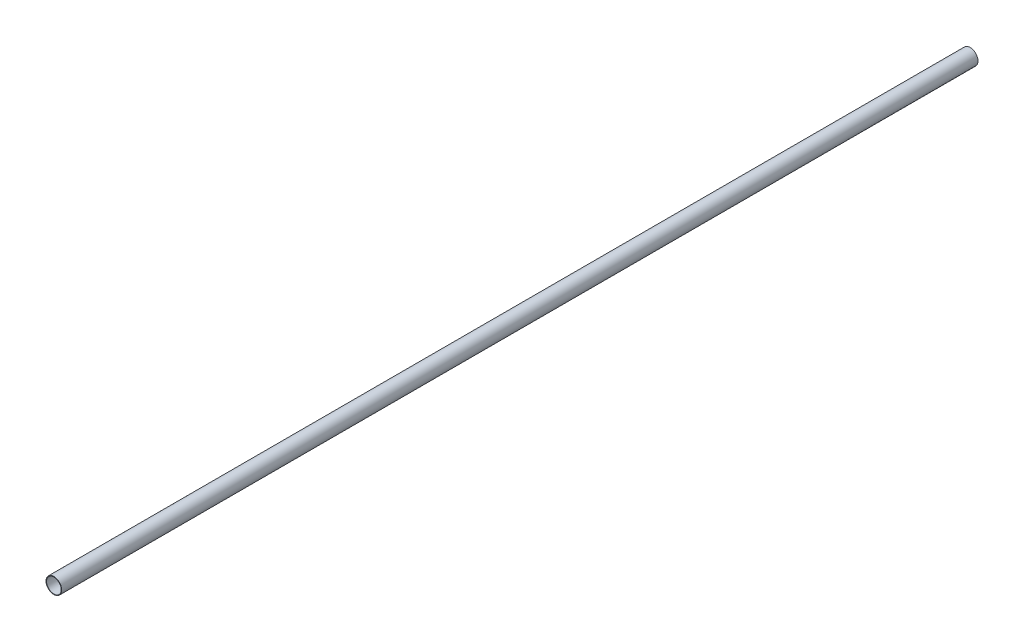
SolidWorks part; units mm, degrees
ref_plane "Спереди" through (0, 0, 0) normal (0, 0, 1) x (1, 0, 0)
ref_plane "Сверху" through (0, 0, 0) normal (0, 1, 0) x (1, 0, 0)
ref_plane "Справа" through (0, 0, 0) normal (1, 0, 0) x (0, 0, -1)
sketch "Эскиз1" plane through (0, 0, 0) normal (0, 0, 1) x (1, 0, 0)
  circle A0 centre (0, 0) radius 2.8
  circle A1 centre (0, 0) radius 3
  dimension "D1" = 6
  dimension "D2" = 0.2
extrude "Бобышка-Вытянуть1" add sketch "Эскиз1" along normal blind 350
